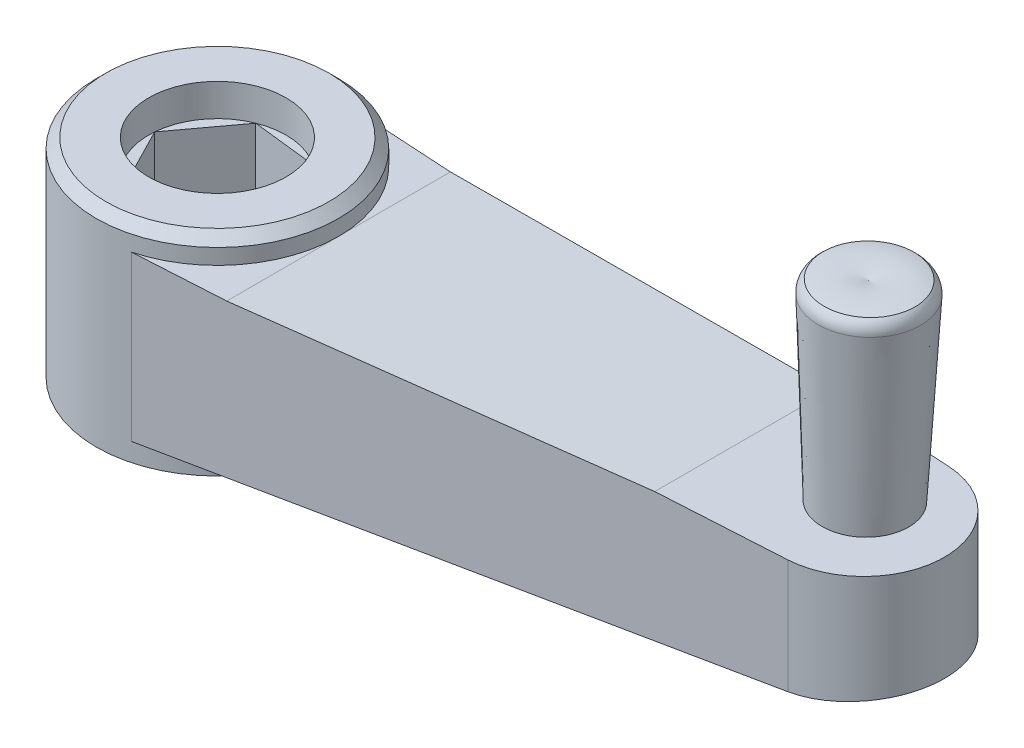
SolidWorks part; units mm, degrees
ref_plane "Plan de face" through (0, 0, 0) normal (0, 0, 1) x (1, 0, 0)
ref_plane "Plan de dessus" through (0, 0, 0) normal (0, 1, 0) x (1, 0, 0)
ref_plane "Plan de droite" through (0, 0, 0) normal (1, 0, 0) x (0, 0, -1)
ref_plane "Plan4" through (0, 26, 0) normal (0, 1, 0) x (-1, 0, 0)
sketch "Esquisse1" plane through (0, 26, 0) normal (0, 1, 0) x (-1, 0, 0)
  line L0 (-0.8636, 14.6746) -> (-80.5875, 9.9827)
  line L1 (-80.5875, -9.9827) -> (-0.8636, -14.6746)
  arc A0 (-0.8636, -14.6746) -> (-0.8636, 14.6746) centre (0, 0) ccw
  arc A1 (-80.5875, 9.9827) -> (-80.5875, -9.9827) centre (-80, 0) ccw
extrude "Boss.-Extru.1" add sketch "Esquisse1" against normal blind 25.7
sketch "Esquisse2" plane through (0, 0, 0) normal (0, 0, 1) x (1, 0, 0)
  line L0 (-21, 22.88) -> (15, 22.88)
  line L1 (15, 22.88) -> (70, 26.31)
  line L2 (70, 26.31) -> (90, 26.31)
  line L3 (90, 26.31) -> (90, 72.8393)
  line L4 (90, 72.8393) -> (-21, 72.8393)
  line L5 (-21, 72.8393) -> (-21, 22.88)
extrude "Enlèv. mat.-Extru.1" cut sketch "Esquisse2" along normal blind 80 and the other way blind 80
sketch "Esquisse3" plane through (0, 0, 0) normal (0, 0, 1) x (1, 0, 0)
  line L0 (-25, -30.1858) -> (90.01, -30.1858)
  line L1 (90.01, -30.1858) -> (90.01, 13)
  line L2 (90.01, 13) -> (-25, -0.8985)
  line L3 (-25, -0.8985) -> (-25, -30.1858)
sketch "Esquisse4" plane through (0, 0, 0) normal (0, 0, 1) x (1, 0, 0)
  line L0 (0, 26) -> (13.8, 26)
  line L1 (13.8, 26) -> (15, 24.8)
  line L2 (15, 24.8) -> (15, 0.3)
  line L3 (15, 0.3) -> (11, 0.3)
  line L4 (11, 0.3) -> (11, 0)
  line L5 (11, 0) -> (0, 0)
  line L6 (0, 0) -> (0, 26)
  line L7 (0, 0) -> (0, 26) construction
extrude "Enlèv. mat.-Extru.2" cut sketch "Esquisse3" along normal blind 80 and the other way blind 80
revolve "Révolution1" add sketch "Esquisse4" angle 360 about L7 reverse direction yes
sketch "Esquisse5" plane through (0, 0, 0) normal (0, 0, 1) x (1, 0, 0)
  line L0 (0, 52) -> (8.5, 52)
  line L1 (8.5, 52) -> (8.5, 22)
  line L2 (8.5, 22) -> (0, 22)
  line L3 (0, 22) -> (0, 52)
  line L4 (0, 22) -> (0, 52) construction
revolve "Enlèvement de matière-Révolution1" cut sketch "Esquisse5" angle 360 about L4 reverse direction yes
ref_plane "Plan5" through (0, 22, 0) normal (0, 1, 0) x (-1, 0, 0)
sketch "Esquisse6" plane through (0, 22, 0) normal (0, 1, 0) x (-1, 0, 0)
  line L2 (0, -7.0992) -> (0, -7.0711)
sketch "Esquisse7" plane through (0, 0, 0) normal (0, 0, 1) x (1, 0, 0)
  line L0 (86.3492, 51) -> (87.1429, 51)
  line L1 (87.1429, 51) -> (85.5556, 27)
  line L2 (85.5556, 27) -> (83, 27)
  line L3 (83, 27) -> (83, 21.1135)
  line L4 (83, 21.1135) -> (82.3865, 20.5)
  line L5 (82.3865, 20.5) -> (80, 20.5)
  line L6 (80, 20.5) -> (80.6626, 51)
  line L7 (80, 20.5) -> (80.6626, 51) construction
  arc A0 (80.6626, 51) -> (86.3492, 51) centre (83.5059, 38.4205) cw
revolve "Révolution2" add sketch "Esquisse7" angle 360 about L7 reverse direction yes
ref_plane "Plan6" through (0, 1, 0) normal (0, 1, 0) x (-1, 0, 0)
sketch "Esquisse9" plane through (0, 26, 0) normal (0, 1, 0) x (-1, 0, 0)
  line L0 (4.3684, 7.2916) -> (-3.6217, 7.6898)
  line L1 (-3.6217, 7.6898) -> (-8.4989, 0.1373)
  line L2 (-8.4989, 0.1373) -> (-4.8487, -6.9814)
  line L3 (-4.8487, -6.9814) -> (3.1513, -7.8943)
  line L4 (3.1513, -7.8943) -> (8.4704, -0.7084)
  line L5 (8.4704, -0.7084) -> (4.3684, 7.2916)
  circle A0 centre (0, 0) radius 8.5 construction
  dimension "D1" = 120
  dimension "D2" = 120
  dimension "D3" = 120
  dimension "D5" = 8
  dimension "D6" = 8
  dimension "D7" = 8
extrude "Enlèv. mat.-Extru.4" cut sketch "Esquisse9" against normal through all
fillet "Congé4" radius 2 1 edges at (74.1885, 51.2814, 0)
